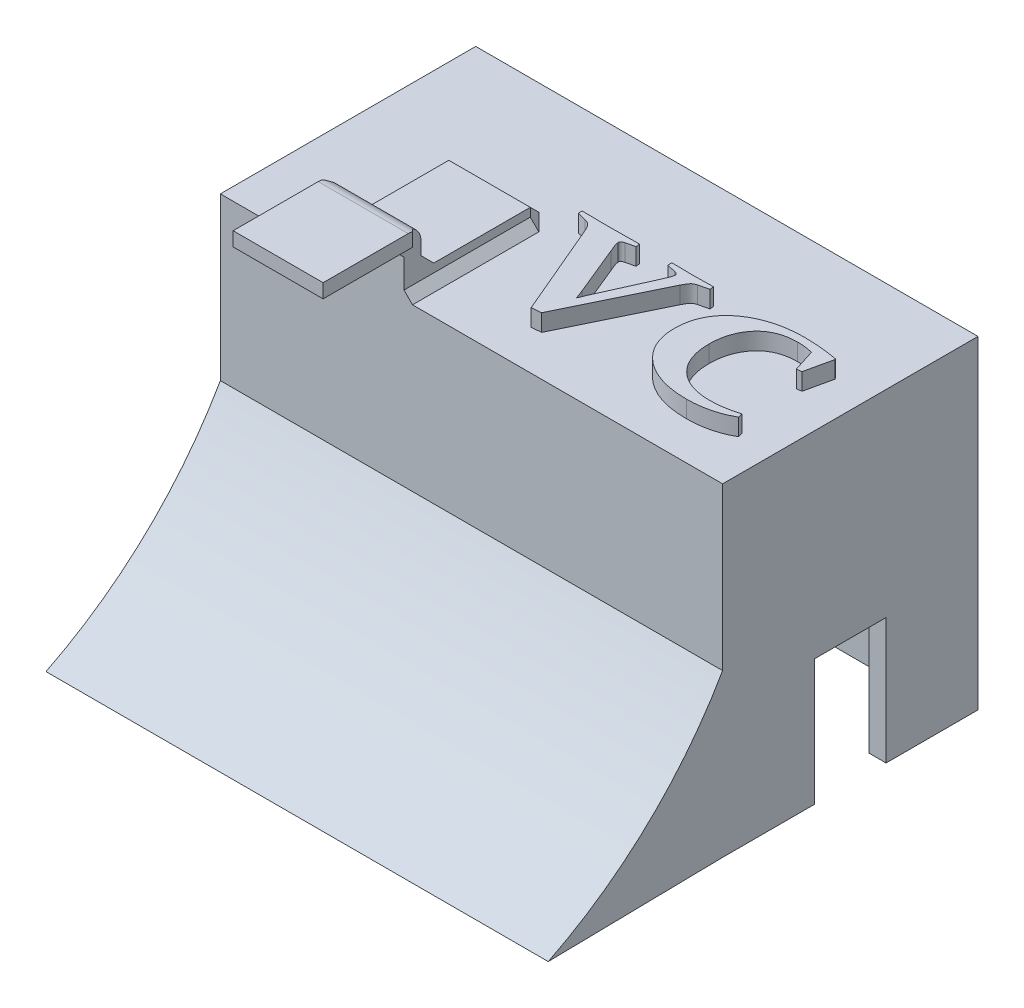
SolidWorks part; units mm, degrees
ref_plane "Front Plane" through (0, 0, 0) normal (0, 0, 1) x (1, 0, 0)
ref_plane "Top Plane" through (0, 0, 0) normal (0, 1, 0) x (1, 0, 0)
ref_plane "Right Plane" through (0, 0, 0) normal (1, 0, 0) x (0, 0, -1)
sketch "Sketch1" plane through (0, 0, 0) normal (0, 1, 0) x (1, 0, 0)
  line L0 (0, -30.9129) -> (0, 25.8244) construction
  line L1 (0, -55) -> (0, 55) construction
  line L4 (-4.786, -8.7803) -> (-4.786, -20.0521)
  line L5 (-4.786, -20.0521) -> (4.786, -20.0521)
  line L6 (4.786, -14.216) -> (4.786, -20.0521)
  line L7 (-4.786, 0.0521) -> (4.786, -20.0521) construction
  line L8 (-4.786, -20.0521) -> (4.786, 0.0521) construction
  arc A1 (-4.786, -8.7803) -> (-9.3654, 3.5056) centre (0, 0) ccw
  arc A2 (-9.3654, 3.5056) -> (-13.891, 5.6603) centre (-11.3484, 5.1706) cw
  arc A3 (4.786, -14.216) -> (-13.891, 5.6603) centre (0, 0) ccw
  point P1 (10, 0)
  point P9 (0, -10)
  point P17 (14.3446, 4.3856)
extrude "Boss-Extrude1" add sketch "Sketch1" along normal blind 8
sketch "Sketch2" plane through (0, 0, 0) normal (0, -1, 0) x (1, 0, 0)
  line L0 (-4.786, 8.7803) -> (-4.786, 20.0521) construction
  line L1 (4.786, 20.0521) -> (-4.786, 20.0521)
  line L2 (4.786, 20.0521) -> (4.786, 30.0521)
  line L3 (4.786, 30.0521) -> (-4.786, 30.0521)
  line L4 (-4.786, 20.0521) -> (-4.786, 30.0521)
  dimension "D1" = 0
  dimension "D2" = 10
extrude "Boss-Extrude2" add sketch "Sketch2" against normal blind 2
sketch "Sketch3" plane through (-4.786, 0, 0) normal (-1, 0, 0) x (0, 0, 1)
  line L0 (30.0521, 2) -> (30.0521, 7)
  line L1 (30.0521, 2) -> (20.0521, 2) construction
  line L2 (28.0521, 2) -> (30.0521, 2)
  line L3 (28.0521, 2) -> (28.0521, 7)
  line L4 (28.0521, 7) -> (30.0521, 7)
  line L5 (30.0521, 2) -> (30.0521, 7)
  line L7 (28.0521, 7) -> (34.0521, 7)
  line L8 (28.0521, 7) -> (28.0521, 5.3521)
  line L9 (28.0521, 5.3521) -> (34.0521, 5.3521)
  line L10 (34.0521, 7) -> (34.0521, 5.3521)
  line M6 (30.0521, 2) -> (20.0521, 2)
  dimension "D1" = 5
  dimension "D2" = 2
  dimension "D3" = 6
extrude "Boss-Extrude3" add sketch "Sketch3" against normal up to vertex contours L9 L3 L0 M6 | L3 L9 L5 L4
fillet "Fillet1" radius 2 1 edges at (0, 7, 28.0521)
fillet "Fillet2" radius 4 1 edges at (0, 8, 20.0521)
fillet "Fillet3" radius 2 2 edges at (10.9313, 8, -10.2717) (9.3702, 8, -3.4926)
sketch "Sketch4" plane through (0, 0, 34.0521) normal (0, 0, 1) x (1, 0, 0)
  line L4 (-4.786, 7) -> (-4.786, 5.3521)
  line L5 (-4.786, 5.3521) -> (4.786, 5.3521)
  line L6 (4.786, 5.3521) -> (4.786, 7)
  line L7 (4.786, 7) -> (-4.786, 7)
  line L8 (-4.786, 7) -> (-4.786, 5.3521)
  line L9 (-4.786, 5.3521) -> (4.786, 5.3521)
  line L10 (4.786, 5.3521) -> (4.786, 7)
  line L11 (4.786, 7) -> (-4.786, 7)
  dimension "D1" = 0
extrude "Boss-Extrude4" add sketch "Sketch4" along normal blind 6
sketch "Sketch5" plane through (0, 7, 0) normal (0, 1, 0) x (1, 0, 0)
  line L1 (4.786, -40.0521) -> (-4.786, -40.0521)
  line L2 (4.786, -40.0521) -> (4.786, -42.0521)
  line L3 (4.786, -42.0521) -> (-4.786, -42.0521)
  line L4 (-4.786, -40.0521) -> (-4.786, -42.0521)
  dimension "D1" = 2
sketch "Sketch6" plane through (0, 0, 20.0521) normal (0, 0, 1) x (1, 0, 0)
  line L0 (-4.786, 2) -> (34.6909, 2)
  line L1 (34.6909, 2) -> (34.2484, 14.8159)
  line L2 (34.2484, 14.8159) -> (-47.3796, 25.1965)
  line L3 (-47.3796, 25.1965) -> (-35.0014, 2)
  line L4 (-35.0014, 2) -> (-4.786, 2)
extrude "Cut-Extrude1" cut sketch "Sketch6" against normal through all
sketch "Sketch7" plane through (0, 2, 0) normal (0, 1, 0) x (1, 0, 0)
  line L0 (4.786, -14.216) -> (-4.786, -14.216)
  line L1 (-4.786, -28.0521) -> (-4.786, -8.7803) construction
  line L2 (-4.786, -14.216) -> (-26.7057, 1.4402)
  line L3 (-26.7057, 1.4402) -> (11.6981, 31.3741)
  line L4 (11.6981, 31.3741) -> (22.2461, -7.8031)
  line L5 (22.2461, -7.8031) -> (8.6558, -15.3655)
  line L6 (8.6558, -15.3655) -> (4.786, -14.216)
extrude "Cut-Extrude2" cut sketch "Sketch7" against normal blind 10
sketch "Sketch8" plane through (0, 0, 0) normal (0, -1, 0) x (1, 0, 0)
  line L4 (-4.786, 30.0521) -> (-4.786, 14.216)
  line L5 (-4.786, 14.216) -> (4.786, 14.216)
  line L6 (4.786, 14.216) -> (4.786, 30.0521)
  line L7 (4.786, 30.0521) -> (-4.786, 30.0521)
  line L8 (-4.786, 30.0521) -> (-4.786, 14.216)
  line L9 (-4.786, 14.216) -> (4.786, 14.216)
  line L10 (4.786, 14.216) -> (4.786, 30.0521)
  line L11 (4.786, 30.0521) -> (-4.786, 30.0521)
  dimension "D1" = 0
sketch "Sketch9" plane through (0, 0, 0) normal (0, -1, 0) x (1, 0, 0)
  line L1 (-4.786, 30.0521) -> (40.214, 30.0521)
  line L3 (-4.786, 4.0521) -> (40.214, 4.0521)
  line L4 (40.214, 30.0521) -> (40.214, 4.0521)
  line L5 (-4.786, 30.0521) -> (-14.786, 30.0521)
  line L7 (-4.786, 4.0521) -> (-14.786, 4.0521)
  line L8 (-14.786, 30.0521) -> (-14.786, 4.0521)
  dimension "D1" = 26
  dimension "D2" = 45
  dimension "D3" = 10
extrude "Boss-Extrude6" add sketch "Sketch9" along normal blind 2
sketch "Sketch10" plane through (0, 0, 0) normal (0, 1, 0) x (1, 0, 0)
  line L0 (-16.786, -2.0521) -> (-16.786, -32.0521)
  line L1 (-14.786, -4.0521) -> (40.214, -4.0521)
  line L2 (-14.786, -4.0521) -> (-14.786, -30.0521)
  line L3 (-14.786, -30.0521) -> (40.214, -30.0521)
  line L4 (40.214, -4.0521) -> (40.214, -30.0521)
  line L5 (-16.786, -32.0521) -> (42.214, -32.0521)
  line L6 (42.214, -2.0521) -> (42.214, -32.0521)
  line L7 (-16.786, -2.0521) -> (42.214, -2.0521)
  dimension "D1" = 2
extrude "Boss-Extrude7" add sketch "Sketch10" against normal blind 38
sketch "Sketch11" plane through (42.214, 0, 0) normal (1, 0, 0) x (0, 0, -1)
  line L0 (-17.0521, -38) -> (-17.0521, 0) construction
  line L1 (-32.0521, -38) -> (-2.0521, -38) construction
  line L3 (-21.2521, -23.2) -> (-12.8521, -23.2)
  line L4 (-21.2521, -23.2) -> (-21.2521, -34)
  line L5 (-21.2521, -34) -> (-12.8521, -34)
  line L6 (-12.8521, -23.2) -> (-12.8521, -34)
  line L7 (-21.2521, -23.2) -> (-12.8521, -34) construction
  line L8 (-21.2521, -34) -> (-12.8521, -23.2) construction
  point P4 (-17.0521, -28.6)
  dimension "D1" = 8.4
  dimension "D2" = 10.8
  dimension "D3" = 4
extrude "Cut-Extrude3" cut sketch "Sketch11" against normal blind 38
sketch "Sketch13" plane through (42.214, 0, 0) normal (1, 0, 0) x (0, 0, -1)
  line L0 (-32.0521, -38) -> (-52.0521, -38)
  line L1 (-32.0521, 0) -> (-32.0521, -38)
  arc A0 (-32.0521, 0) -> (-52.0521, -38) centre (-90.5843, 6.5433) cw
  dimension "D1" = 20
extrude "Boss-Extrude8" add sketch "Sketch13" against normal up to surface (59 mm away) up to face at (-16.786, -19, 17.0521)
sketch "Sketch14" plane through (0, 7, 0) normal (0, 1, 0) x (1, 0, 0)
  line L4 (-4.786, -30.0521) -> (-5.786, -30.0521)
  line L5 (-5.786, -30.0521) -> (5.786, -30.0521)
  line L6 (4.786, -40.0521) -> (5.786, -40.0521)
  line L7 (5.786, -40.0521) -> (-5.786, -40.0521)
  line L8 (5.786, -41.0521) -> (5.786, -29.0521)
  line L9 (5.786, -29.0521) -> (-5.786, -29.0521)
  line L10 (-5.786, -29.0521) -> (-5.786, -41.0521)
  line L11 (-5.786, -41.0521) -> (5.786, -41.0521)
  line L12 (5.786, -40.0521) -> (5.786, -30.0521)
  line L14 (-5.786, -30.0521) -> (-5.786, -40.0521)
  line M5 (4.786, -40.0521) -> (4.786, -30.0521)
  line M7 (-4.786, -30.0521) -> (-4.786, -40.0521)
  dimension "D1" = 1
extrude "Boss-Extrude9" add sketch "Sketch14" against normal up to surface (1.6479 mm away) contours L4 L14 L7 M7 | L6 L12 L5 M5 up to face at (0, 5.3521, 35.0521)
chamfer "Chamfer1" distance 1 angle 45 4 edges at (-4.786, 6.176, 30.0521) (-5.286, 5.3521, 30.0521) (5.286, 5.3521, 30.0521) (4.786, 6.176, 30.0521)
chamfer "Chamfer2" distance 1 angle 45 6 edges at (-4.786, 0, 22.134) (4.786, 0, 22.134) (0, 2, 14.216) (0, 0, 14.216) (4.786, 1, 14.216) (-4.786, 1, 14.216)
sketch "Sketch15" plane through (0, 0, 0) normal (0, 1, 0) x (1, 0, 0)
  line L0 (42.214, -25.2308) -> (8.373, -25.2308) construction
  line L1 (42.214, -32.0521) -> (42.214, -2.0521) construction
  text T0 "VC" font "Constantia" height in points 48
extrude "Boss-Extrude10" add sketch "Sketch15" along normal blind 2
chamfer "Chamfer4" distance 1 angle 45 1 edges at (0, 5.3521, 30.0521)
sketch "Sketch16" plane through (42.214, 0, 0) normal (1, 0, 0) x (0, 0, -1)
  line L0 (-52.0521, -38) -> (-2.0521, -38) construction
  line L1 (-12.8521, -34) -> (-21.2521, -34)
  line L2 (-12.8521, -34) -> (-12.8521, -38)
  line L3 (-12.8521, -38) -> (-21.2521, -38)
  line L4 (-21.2521, -34) -> (-21.2521, -38)
extrude "Cut-Extrude4" cut sketch "Sketch16" against normal blind 10
sketch "Sketch17" plane through (0, 7, 0) normal (0, 1, 0) x (1, 0, 0)
  line L4 (-5.286, -30.5521) -> (-5.286, -27.1076)
  line L5 (-5.286, -27.1076) -> (-11.1953, -28.1806)
  line L6 (-11.1953, -28.1806) -> (-7.6295, -44.4406)
  line L7 (-7.6295, -44.4406) -> (-5.286, -41.3937)
  line L8 (-5.286, -39.5521) -> (5.286, -39.5521)
  line L9 (5.286, -39.5521) -> (5.286, -30.5521)
  line L10 (5.286, -30.5521) -> (-5.286, -30.5521)
  line L11 (-5.286, -30.5521) -> (-5.286, -39.5521)
  line L13 (5.286, -39.5521) -> (5.286, -30.5521)
  line L15 (-5.286, -30.5521) -> (-5.286, -39.5521)
  line L16 (-5.286, -41.3937) -> (-5.286, -39.5521)
  line L17 (5.286, -30.5521) -> (5.286, -27.1076)
  line L18 (5.286, -27.1076) -> (12.9604, -35.4231)
  line L19 (12.9604, -35.4231) -> (6.255, -43.0761)
  line L20 (6.255, -43.0761) -> (5.286, -41.0132)
  line L21 (5.286, -41.0132) -> (5.286, -39.5521)
  dimension "D1" = 0.5
extrude "Cut-Extrude5" cut sketch "Sketch17" against normal blind 2
sketch "Sketch18" plane through (0, 0, 0) normal (0, 1, 0) x (1, 0, 0)
  line L0 (-5.786, -30.0521) -> (-16.786, -30.0521)
  line L1 (-16.786, -2.0521) -> (-16.786, -32.0521) construction
  line L2 (-16.786, -30.0521) -> (-16.786, -32.0521)
  line L4 (42.214, -32.0521) -> (42.214, -30.0521)
  line L5 (42.214, -32.0521) -> (42.214, -2.0521) construction
  line L6 (42.214, -30.0521) -> (-5.786, -30.0521)
  line L8 (-16.786, -32.0521) -> (42.214, -32.0521)
  line L9 (-16.786, -32.0521) -> (-16.786, -37.3443)
  line L10 (-16.786, -37.3443) -> (42.214, -37.3443)
  line L11 (42.214, -32.0521) -> (42.214, -37.3443)
  line M45 (-16.786, -2.0521) -> (-16.786, -32.0521)
  line M46 (-16.786, -32.0521) -> (42.214, -32.0521)
  line M47 (42.214, -32.0521) -> (42.214, -2.0521)
  line M48 (5.786, -30.0521) -> (-5.786, -30.0521)
extrude "Cut-Extrude6" cut sketch "Sketch18" against normal blind 10 contours L11 L9 L10 M46 | L6 L0 M47 M48 M45 M46
sketch "Sketch20" plane through (0, -2, 0) normal (0, -1, 0) x (1, 0, 0)
  line L0 (-14.786, 30.0521) -> (-14.786, 4.0521) construction
  line L1 (40.214, 30.0521) -> (-14.786, 30.0521)
  line L2 (40.214, 30.0521) -> (40.214, 28.0521)
  line L3 (40.214, 28.0521) -> (-14.786, 28.0521)
  line L4 (-14.786, 30.0521) -> (-14.786, 28.0521)
  dimension "D1" = 2
extrude "Boss-Extrude11" add sketch "Sketch20" along normal up to surface (36 mm away) up to face at (22.214, -38, 20.3854)
sketch "Sketch21" plane through (0, -38, 0) normal (0, -1, 0) x (1, 0, 0)
  line L0 (42.214, 2.0521) -> (-16.786, 2.0521) construction
  line L1 (40.214, 4.0521) -> (-14.786, 4.0521)
  line L2 (40.214, 4.0521) -> (40.214, 2.0521)
  line L3 (40.214, 2.0521) -> (-14.786, 2.0521)
  line L4 (-14.786, 4.0521) -> (-14.786, 2.0521)
extrude "Cut-Extrude7" cut sketch "Sketch21" against normal up to surface (36 mm away) up to face at (12.714, -2, 16.0521)
sketch "Sketch22" plane through (42.214, 0, 0) normal (1, 0, 0) x (0, 0, -1)
  line L0 (-12.8521, -38) -> (-2.0521, -38) construction
  line L1 (-12.8521, -23.2) -> (-10.8521, -23.2)
  line L2 (-12.8521, -23.2) -> (-12.8521, -38)
  line L3 (-12.8521, -38) -> (-10.8521, -38)
  line L4 (-10.8521, -23.2) -> (-10.8521, -38)
  dimension "D1" = 2
extrude "Cut-Extrude8" cut sketch "Sketch22" against normal blind 10
sketch "Sketch23" plane through (42.214, 0, 0) normal (1, 0, 0) x (0, 0, -1)
  line L1 (-21.2521, -23.2) -> (-19.2521, -23.2)
  line L2 (-21.2521, -23.2) -> (-21.2521, -38)
  line L3 (-21.2521, -38) -> (-19.2521, -38)
  line L4 (-19.2521, -23.2) -> (-19.2521, -38)
  dimension "D1" = 2
extrude "Boss-Extrude12" add sketch "Sketch23" against normal up to surface (2 mm away) up to face at (40.214, -25.3, 15.5521)
sketch "Sketch24" plane through (0, 0, 0) normal (0, 1, 0) x (1, 0, 0)
  line L0 (-16.786, -2.0521) -> (-16.786, -30.0521) construction
  line L1 (42.214, -2.0521) -> (-16.786, -2.0521)
  line L2 (42.214, -2.0521) -> (42.214, -0.0521)
  line L3 (42.214, -0.0521) -> (-16.786, -0.0521)
  line L4 (-16.786, -2.0521) -> (-16.786, -0.0521)
  dimension "D1" = 0
  dimension "D2" = 2
extrude "Boss-Extrude13" add sketch "Sketch24" against normal up to surface (38 mm away) up to face at (12.714, -38, 25.3521)
sketch "Sketch25" plane through (0, -10, 0) normal (0, 1, 0) x (1, 0, 0)
  line L4 (42.214, -34.0586) -> (42.214, -30.0521)
  line L5 (42.214, -30.0521) -> (-16.786, -30.0521)
  line L6 (-16.786, -30.0521) -> (-16.786, -34.0586)
  line L7 (-16.786, -34.0586) -> (42.214, -34.0586)
  line L8 (42.214, -34.0586) -> (42.214, -30.0521)
  line L9 (42.214, -30.0521) -> (-16.786, -30.0521)
  line L10 (-16.786, -30.0521) -> (-16.786, -34.0586)
  line L11 (-16.786, -34.0586) -> (42.214, -34.0586)
  dimension "D1" = 0
sketch "Sketch26" plane through (0, -38, 0) normal (0, -1, 0) x (1, 0, 0)
  line L0 (-16.786, 0.0521) -> (-16.786, 52.0521) construction
  line L1 (42.214, 52.0521) -> (-16.786, 52.0521)
  line L2 (42.214, 52.0521) -> (42.214, 30.0521)
  line L3 (42.214, 30.0521) -> (-16.786, 30.0521)
  line L4 (-16.786, 52.0521) -> (-16.786, 30.0521)
  line L5 (-14.786, 28.0521) -> (40.214, 28.0521) construction
  dimension "D1" = 2
extrude "Cut-Extrude12" cut sketch "Sketch26" against normal blind 31
sketch "Sketch27" plane through (42.214, 0, 0) normal (1, 0, 0) x (0, 0, -1)
  line L0 (-30.0521, -38) -> (-50.5331, -38.3608)
  line L1 (-30.0521, -38) -> (-30.0521, 0) construction
  line L2 (-30.0521, -19) -> (-30.0521, -38)
  arc A0 (-50.5331, -38.3608) -> (-30.0521, -19) centre (-72.2239, 5.0984) ccw
extrude "Boss-Extrude14" add sketch "Sketch27" against normal up to surface (59 mm away) up to face at (-16.786, -19, 15.0521)
chamfer "Chamfer5" distance 1.5 angle 45 1 edges at (0, 2, 28.0521)
